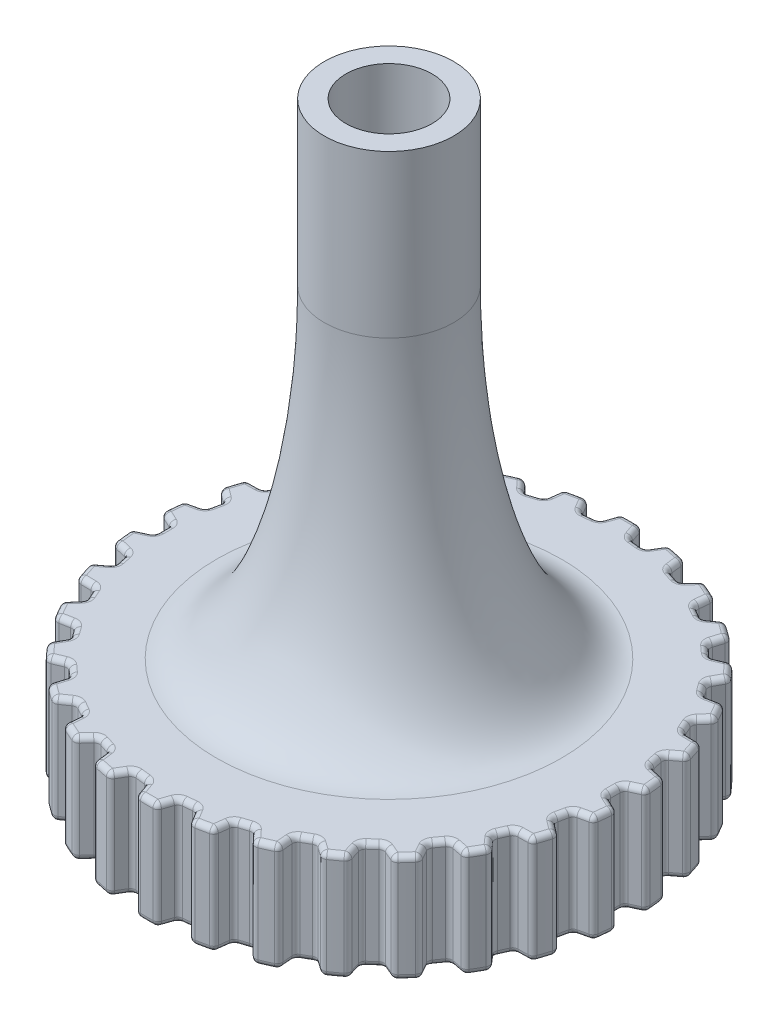
SolidWorks part; units mm, degrees
ref_plane "Płaszczyzna przednia" through (0, 0, 0) normal (0, 0, 1) x (1, 0, 0)
ref_plane "Płaszczyzna górna" through (0, 0, 0) normal (0, 1, 0) x (1, 0, 0)
ref_plane "Płaszczyzna prawa" through (0, 0, 0) normal (1, 0, 0) x (0, 0, -1)
sketch "Szkic1" plane through (0, 0, 0) normal (0, 0, 1) x (1, 0, 0)
  line L0 (0, -45) -> (0, -55)
  line L2 (6, -45) -> (6, 0)
  line L3 (6, 0) -> (4, 0)
  line L4 (4, 0) -> (4, -45)
  line L5 (4, -45) -> (0, -45)
  line L6 (0, 0) -> (0, 10.5699) construction
  line L9 (6, -45) -> (22.5, -45)
  line L10 (22.5, -45) -> (22.5, -55)
  line L11 (22.5, -55) -> (0, -55)
  dimension "D5" = 10
  dimension "D1" = 8
  dimension "D2" = 45
  dimension "D3" = 12
  dimension "D4" = 10
  dimension "D6" = 45
revolve "Obrót1" add sketch "Szkic1" angle 360 about L6
fillet "Zaokrąglenie1" radius 30 1 edges at (0, -45, -6) second distance 10 first distance on face at (0, 0, -6)
sketch "Szkic2" plane through (0, -55, 0) normal (0, -1, 0) x (-1, 0, 0)
  line L0 (19.9549, 0) -> (25.9475, 0) construction
  line L1 (23.5, 1.9158) -> (21, 0.75)
  line L2 (21, 0.75) -> (21, -0.75)
  line L3 (21, -0.75) -> (23.5, -1.9158)
  line L4 (23.5, -1.9158) -> (23.5, 1.9158)
  circle A0 centre (0, 0) radius 22.5 construction
  arc A1 (22.4546, -1.4283) -> (22.4546, 1.4283) centre (0, 0) ccw construction
  point P5 (23.5, 0)
  dimension "D1" = 21
  dimension "D4" = 2.5
  dimension "D2" = 1.5
  dimension "D3" = 25
extrude "Wytnij-wyciągnięcie1" cut sketch "Szkic2" against normal up to surface (10 mm away)
fillet "Zaokrąglenie2" radius 0.5 4 edges at (-22.4546, -50, 1.4283) (-22.4546, -50, -1.4283) (-21, -50, -0.75) (-21, -50, 0.75)
pattern_circular "Szyk kołowy1" count 30 over 360 about axis through (0, -55, 0) along (0, -1, 0) of "Zaokrąglenie2", "Wytnij-wyciągnięcie1"
fillet "Zaokrąglenie3" radius 0.5 400 edges at (-9.9193, -45, 19.3482) (-9.9328, -45, 18.6044) (-10.5, -45, 18.1865) (-11.1455, -45, 17.9043) (-11.7964, -45, 18.2645) (-12.4671, -45, 18.6251) (-13.2252, -45, 18.2029) (-13.861, -45, 17.6124) (-13.7253, -45, 16.8631) (-13.5839, -45, 16.1327) (-14.0517, -45, 15.606) (-14.6244, -45, 15.1958) (-15.336, -45, 15.4127) (-16.067, -45, 15.6261) (-16.7208, -45, 15.0554) (-17.2199, -45, 14.3456) (-16.9314, -45, 13.6409) (-16.6412, -45, 12.9559) (-16.9894, -45, 12.3435) (-17.4642, -45, 11.8231) (-18.2054, -45, 11.8874) (-18.9648, -45, 11.9441) (-19.4856, -45, 11.25) (-19.8263, -45, 10.4519) (-19.3975, -45, 9.8226) (-18.9712, -45, 9.2129) (-19.1845, -45, 8.5415) (-19.5408, -45, 7.9337) (-20.2791, -45, 7.8425) (-21.0336, -45, 7.7401) (-21.3988, -45, 6.9529) (-21.5661, -45, 6.1014) (-21.0158, -45, 5.575) (-20.4721, -45, 5.0672) (-20.5411, -45, 4.3661) (-20.7633, -45, 3.6976) (-21.4665, -45, 3.4549) (-22.1833, -45, 3.1978) (-22.3767, -45, 2.3519) (-22.3634, -45, 1.4842) (-21.7157, -45, 1.0837) (-21.0783, -45, 0.7001) (-21, -45, 0) (-21.0783, -45, -0.7001) (-21.7157, -45, -1.0837) (-22.3634, -45, -1.4842) (-22.3767, -45, -2.3519) (-22.1833, -45, -3.1978) (-21.4665, -45, -3.4549) (-20.7633, -45, -3.6976) (-20.5411, -45, -4.3661) (-20.4721, -45, -5.0672) (-21.0158, -45, -5.575) (-21.5661, -45, -6.1014) (-21.3988, -45, -6.9529) (-21.0336, -45, -7.7401) (-20.2791, -45, -7.8425) (-19.5408, -45, -7.9337) (-19.1845, -45, -8.5415) (-18.9712, -45, -9.2129) (-19.3975, -45, -9.8226) (-19.8263, -45, -10.4519) (-19.4856, -45, -11.25) (-18.9648, -45, -11.9441) (-18.2054, -45, -11.8874) (-17.4642, -45, -11.8231) (-16.9894, -45, -12.3435) (-16.6412, -45, -12.9559) (-16.9314, -45, -13.6409) (-17.2199, -45, -14.3456) (-16.7208, -45, -15.0554) (-16.067, -45, -15.6261) (-15.336, -45, -15.4127) (-14.6244, -45, -15.1958) (-14.0517, -45, -15.606) (-13.5839, -45, -16.1327) (-13.7253, -45, -16.8631) (-13.861, -45, -17.6124) (-13.2252, -45, -18.2029) (-12.4671, -45, -18.6251) (-11.7964, -45, -18.2645) (-11.1455, -45, -17.9043) (-10.5, -45, -18.1865) (-9.9328, -45, -18.6044) (-9.9193, -45, -19.3482) (-9.8963, -45, -20.1094) (-9.1516, -45, -20.5548) (-8.3222, -45, -20.8102) (-7.7412, -45, -20.318) (-7.1794, -45, -19.8303) (-6.4894, -45, -19.9722) (-5.8477, -45, -20.263) (-5.6798, -45, -20.9878) (-5.4991, -45, -21.7275) (-4.678, -45, -22.0083) (-3.8137, -45, -22.0857) (-3.3477, -45, -21.4835) (-2.8996, -45, -20.8897) (-2.1951, -45, -20.885) (-1.507, -45, -21.036) (-1.1921, -45, -21.71) (-0.8615, -45, -22.396) (0, -45, -22.5) (0.8615, -45, -22.396) (1.1921, -45, -21.71) (1.507, -45, -21.036) (2.1951, -45, -20.885) (2.8996, -45, -20.8897) (3.3477, -45, -21.4835) (3.8137, -45, -22.0857) (4.678, -45, -22.0083) (5.4991, -45, -21.7275) (5.6798, -45, -20.9878) (5.8477, -45, -20.263) (6.4894, -45, -19.9722) (7.1794, -45, -19.8303) (7.7412, -45, -20.318) (8.3222, -45, -20.8102) (9.1516, -45, -20.5548) (9.8963, -45, -20.1094) (9.9193, -45, -19.3482) (9.9328, -45, -18.6044) (10.5, -45, -18.1865) (11.1455, -45, -17.9043) (11.7964, -45, -18.2645) (12.4671, -45, -18.6251) (13.2252, -45, -18.2029) (13.861, -45, -17.6124) (13.7253, -45, -16.8631) (13.5839, -45, -16.1327) (14.0517, -45, -15.606) (14.6244, -45, -15.1958) (15.336, -45, -15.4127) (16.067, -45, -15.6261) (16.7208, -45, -15.0554) (17.2199, -45, -14.3456) (16.9314, -45, -13.6409) (16.6412, -45, -12.9559) (16.9894, -45, -12.3435) (17.4642, -45, -11.8231) (18.2054, -45, -11.8874) (18.9648, -45, -11.9441) (19.4856, -45, -11.25) (19.8263, -45, -10.4519) (19.3975, -45, -9.8226) (18.9712, -45, -9.2129) (19.1845, -45, -8.5415) (19.5408, -45, -7.9337) (20.2791, -45, -7.8425) (21.0336, -45, -7.7401) (21.3988, -45, -6.9529) (21.5661, -45, -6.1014) (21.0158, -45, -5.575) (20.4721, -45, -5.0672) (20.5411, -45, -4.3661) (20.7633, -45, -3.6976) (21.4665, -45, -3.4549) (22.1833, -45, -3.1978) (22.3767, -45, -2.3519) (22.3634, -45, -1.4842) (21.7157, -45, -1.0837) (21.0783, -45, -0.7001) (21, -45, 0) (21.0783, -45, 0.7001) (21.7157, -45, 1.0837) (22.3634, -45, 1.4842) (22.3767, -45, 2.3519) (22.1833, -45, 3.1978) (21.4665, -45, 3.4549) (20.7633, -45, 3.6976) (20.5411, -45, 4.3661) (20.4721, -45, 5.0672) (21.0158, -45, 5.575) (21.5661, -45, 6.1014) (21.3988, -45, 6.9529) (21.0336, -45, 7.7401) (20.2791, -45, 7.8425) (19.5408, -45, 7.9337) (19.1845, -45, 8.5415) (18.9712, -45, 9.2129) (19.3975, -45, 9.8226) (19.8263, -45, 10.4519) (19.4856, -45, 11.25) (18.9648, -45, 11.9441) (18.2054, -45, 11.8874) (17.4642, -45, 11.8231) (16.9894, -45, 12.3435) (16.6412, -45, 12.9559) (16.9314, -45, 13.6409) (17.2199, -45, 14.3456) (16.7208, -45, 15.0554) (16.067, -45, 15.6261) (15.336, -45, 15.4127) (14.6244, -45, 15.1958) (14.0517, -45, 15.606) (13.5839, -45, 16.1327) (13.7253, -45, 16.8631) (13.861, -45, 17.6124) (13.2252, -45, 18.2029) (12.4671, -45, 18.6251) (11.7964, -45, 18.2645) (11.1455, -45, 17.9043) (10.5, -45, 18.1865) (9.9328, -45, 18.6044) (9.9193, -45, 19.3482) (9.8963, -45, 20.1094) (9.1516, -45, 20.5548) (8.3222, -45, 20.8102) (7.7412, -45, 20.318) (7.1794, -45, 19.8303) (6.4894, -45, 19.9722) (5.8477, -45, 20.263) (5.6798, -45, 20.9878) (5.4991, -45, 21.7275) (4.678, -45, 22.0083) (3.8137, -45, 22.0857) (3.3477, -45, 21.4835) (2.8996, -45, 20.8897) (2.1951, -45, 20.885) (1.507, -45, 21.036) (1.1921, -45, 21.71) (0.8615, -45, 22.396) (0, -45, 22.5) (-0.8615, -45, 22.396) (-1.1921, -45, 21.71) (-1.507, -45, 21.036) (-2.1951, -45, 20.885) (-2.8996, -45, 20.8897) (-3.3477, -45, 21.4835) (-3.8137, -45, 22.0857) (-4.678, -45, 22.0083) (-5.4991, -45, 21.7275) (-5.6798, -45, 20.9878) (-5.8477, -45, 20.263) (-6.4894, -45, 19.9722) (-7.1794, -45, 19.8303) (-7.7412, -45, 20.318) (-8.3222, -45, 20.8102) (-9.1516, -45, 20.5548) (-7.1794, -55, 19.8303) (-7.7412, -55, 20.318) (-8.3222, -55, 20.8102) (-9.1516, -55, 20.5548) (-9.8963, -55, 20.1094) (-9.9193, -55, 19.3482) (-9.9328, -55, 18.6044) (-10.5, -55, 18.1865) (-11.1455, -55, 17.9043) (-11.7964, -55, 18.2645) (-12.4671, -55, 18.6251) (-13.2252, -55, 18.2029) (-13.861, -55, 17.6124) (-13.7253, -55, 16.8631) (-13.5839, -55, 16.1327) (-14.0517, -55, 15.606) (-14.6244, -55, 15.1958) (-15.336, -55, 15.4127) (-16.067, -55, 15.6261) (-16.7208, -55, 15.0554) (-17.2199, -55, 14.3456) (-16.9314, -55, 13.6409) (-16.6412, -55, 12.9559) (-16.9894, -55, 12.3435) (-17.4642, -55, 11.8231) (-18.2054, -55, 11.8874) (-18.9648, -55, 11.9441) (-19.4856, -55, 11.25) (-19.8263, -55, 10.4519) (-19.3975, -55, 9.8226) (-18.9712, -55, 9.2129) (-19.1845, -55, 8.5415) (-19.5408, -55, 7.9337) (-20.2791, -55, 7.8425) (-21.0336, -55, 7.7401) (-21.3988, -55, 6.9529) (-21.5661, -55, 6.1014) (-21.0158, -55, 5.575) (-20.4721, -55, 5.0672) (-20.5411, -55, 4.3661) (-20.7633, -55, 3.6976) (-21.4665, -55, 3.4549) (-22.1833, -55, 3.1978) (-22.3767, -55, 2.3519) (-22.3634, -55, 1.4842) (-21.7157, -55, 1.0837) (-21.0783, -55, 0.7001) (-21, -55, 0) (-21.0783, -55, -0.7001) (-21.7157, -55, -1.0837) (-22.3634, -55, -1.4842) (-22.3767, -55, -2.3519) (-22.1833, -55, -3.1978) (-21.4665, -55, -3.4549) (-20.7633, -55, -3.6976) (-20.5411, -55, -4.3661) (-20.4721, -55, -5.0672) (-21.0158, -55, -5.575) (-21.5661, -55, -6.1014) (-21.3988, -55, -6.9529) (-21.0336, -55, -7.7401) (-20.2791, -55, -7.8425) (-19.5408, -55, -7.9337) (-19.1845, -55, -8.5415) (-18.9712, -55, -9.2129) (-19.3975, -55, -9.8226) (-19.8263, -55, -10.4519) (-19.4856, -55, -11.25) (-18.9648, -55, -11.9441) (-18.2054, -55, -11.8874) (-17.4642, -55, -11.8231) (-16.9894, -55, -12.3435) (-16.6412, -55, -12.9559) (-16.9314, -55, -13.6409) (-17.2199, -55, -14.3456) (-16.7208, -55, -15.0554) (-16.067, -55, -15.6261) (-15.336, -55, -15.4127) (-14.6244, -55, -15.1958) (-14.0517, -55, -15.606) (-13.5839, -55, -16.1327) (-13.7253, -55, -16.8631) (-13.861, -55, -17.6124) (-13.2252, -55, -18.2029) (-12.4671, -55, -18.6251) (-11.7964, -55, -18.2645) (-11.1455, -55, -17.9043) (-10.5, -55, -18.1865) (-9.9328, -55, -18.6044) (-9.9193, -55, -19.3482) (-9.8963, -55, -20.1094) (-9.1516, -55, -20.5548) (-8.3222, -55, -20.8102) (-7.7412, -55, -20.318) (-7.1794, -55, -19.8303) (-6.4894, -55, -19.9722) (-5.8477, -55, -20.263) (-5.6798, -55, -20.9878) (-5.4991, -55, -21.7275) (-4.678, -55, -22.0083) (-3.8137, -55, -22.0857) (-3.3477, -55, -21.4835) (-2.8996, -55, -20.8897) (-2.1951, -55, -20.885) (-1.507, -55, -21.036) (-1.1921, -55, -21.71) (-0.8615, -55, -22.396) (0, -55, -22.5) (0.8615, -55, -22.396) (1.1921, -55, -21.71) (1.507, -55, -21.036) (2.1951, -55, -20.885) (2.8996, -55, -20.8897) (3.3477, -55, -21.4835) (3.8137, -55, -22.0857) (4.678, -55, -22.0083) (5.4991, -55, -21.7275) (5.6798, -55, -20.9878) (5.8477, -55, -20.263) (6.4894, -55, -19.9722) (7.1794, -55, -19.8303) (7.7412, -55, -20.318) (8.3222, -55, -20.8102) (9.1516, -55, -20.5548) (9.8963, -55, -20.1094) (9.9193, -55, -19.3482) (9.9328, -55, -18.6044) (10.5, -55, -18.1865) (11.1455, -55, -17.9043) (11.7964, -55, -18.2645) (12.4671, -55, -18.6251) (13.2252, -55, -18.2029) (13.861, -55, -17.6124) (13.7253, -55, -16.8631) (13.5839, -55, -16.1327) (14.0517, -55, -15.606) (14.6244, -55, -15.1958) (15.336, -55, -15.4127) (16.067, -55, -15.6261) (16.7208, -55, -15.0554) (17.2199, -55, -14.3456) (16.9314, -55, -13.6409) (16.6412, -55, -12.9559) (16.9894, -55, -12.3435) (17.4642, -55, -11.8231) (18.2054, -55, -11.8874) (18.9648, -55, -11.9441) (19.4856, -55, -11.25) (19.8263, -55, -10.4519) (19.3975, -55, -9.8226) (18.9712, -55, -9.2129) (19.1845, -55, -8.5415) (19.5408, -55, -7.9337) (20.2791, -55, -7.8425) (21.0336, -55, -7.7401) (21.3988, -55, -6.9529) (21.5661, -55, -6.1014) (21.0158, -55, -5.575) (20.4721, -55, -5.0672) (20.5411, -55, -4.3661) (20.7633, -55, -3.6976)
